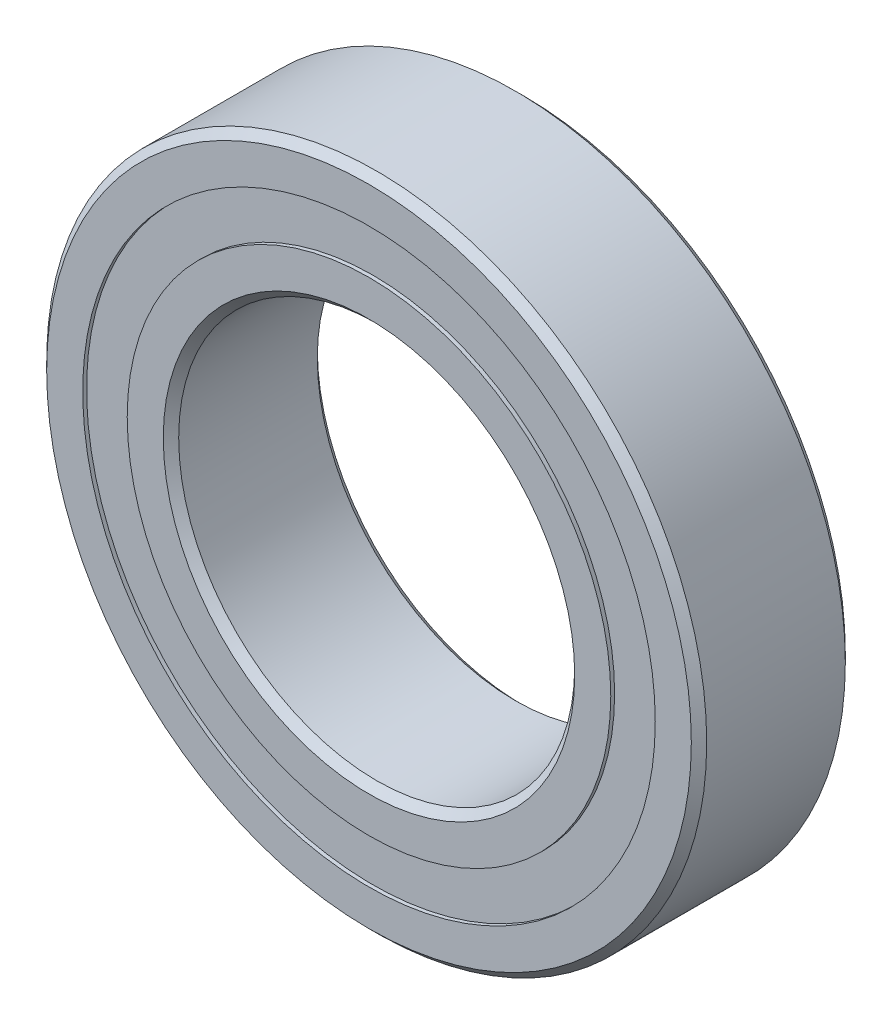
SolidWorks part; units mm, degrees
ref_plane "Front Plane" through (0, 0, 0) normal (0, 0, 1) x (1, 0, 0)
ref_plane "Top Plane" through (0, 0, 0) normal (0, 1, 0) x (1, 0, 0)
ref_plane "Right Plane" through (0, 0, 0) normal (1, 0, 0) x (0, 0, -1)
sketch "Sketch1" plane through (0, 0, 0) normal (1, 0, 0) x (0, 0, -1)
  line L0 (-3.5, 0) -> (3.5, 0) construction
  line L1 (0, 15) -> (0, -15) construction
  line L2 (3.15, 15) -> (-3.15, 15)
  line L3 (-3.15, 15) -> (-3.5, 14.65)
  line L4 (-3.5, 14.65) -> (-3.5, 13.011)
  line L5 (-3.5, 13.011) -> (-1.5556, 13.011)
  line L6 (3.5, 13.011) -> (1.5556, 13.011)
  line L7 (3.5, 14.65) -> (3.5, 13.011)
  line L8 (3.15, 15) -> (3.5, 14.65)
  line L9 (0, 15) -> (0, 12) construction
  line L10 (0, 12) -> (0, 9) construction
  arc A0 (-1.5556, 13.011) -> (1.5556, 13.011) centre (0, 12) cw
  point P14 (0, 9)
  dimension "Width" = 7
  dimension "OD" = 30
  dimension "D1" = 45
  dimension "D2" = 0.35
  dimension "Shaft Dia" = 18
  dimension "D3" = 3.1111
  dimension "D4" = 1.011
revolve "Revolve1" add sketch "Sketch1" angle 360 about L0
sketch "Sketch3" plane through (0, 0, 0) normal (1, 0, 0) x (0, 0, -1)
  line L0 (-3.5, 10.989) -> (-1.5556, 10.989)
  line L1 (0, 15) -> (0, -15) construction
  line L2 (-3.5, 14.65) -> (-3.5, 13.011) construction
  line L3 (-3.5, 10.989) -> (-3.5, 9.35)
  line L4 (-3.15, 15) -> (-3.5, 14.65) construction
  line L5 (-3.5, 9.35) -> (-3.15, 9)
  line L6 (-3.15, 9) -> (3.15, 9)
  line L7 (3.15, 15) -> (3.15, -15) construction
  line L8 (3.15, 9) -> (3.5, 9.35)
  line L9 (3.5, -14.65) -> (3.5, 14.65) construction
  line L10 (3.5, 9.35) -> (3.5, 10.989)
  line L11 (3.5, 10.989) -> (1.5556, 10.989)
  line L13 (3.15, 15) -> (3.5, 14.65) construction
  arc A0 (1.5556, 13.011) -> (-1.5556, 13.011) centre (0, 12) ccw construction
  arc A1 (1.5556, 10.989) -> (-1.5556, 10.989) centre (0, 12) cw
revolve "Revolve3" add sketch "Sketch3" angle 360 about L0
sketch "Sketch4" plane through (0, 0, 0) normal (1, 0, 0) x (0, 0, -1)
  line L0 (-1.8552, 12) -> (1.8552, 12)
  arc A2 (-1.8552, 12) -> (1.8552, 12) centre (0, 12) cw
  arc A3 (1.5556, 13.011) -> (-1.5556, 13.011) centre (0, 12) ccw construction
revolve "Revolve4" add sketch "Sketch4" angle 360 about L0
ref_axis "Axis1" through (0, 0, -3.5) along (0, 0, 1)
pattern_circular "CirPattern1" count 12 every 30 about axis through (0, 0, -3.5) along (0, 0, 1) of bodies 104
sketch "Sketch5" plane through (0, 0, 0) normal (1, 0, 0) x (0, 0, -1)
  line L0 (-3.5, 13.011) -> (-1.5556, 13.011) construction
  line L1 (-3.325, 13.011) -> (-1.8552, 13.011)
  line L2 (-3.325, 13.011) -> (-3.325, 10.989)
  line L3 (-3.325, 10.989) -> (-1.8552, 10.989)
  line L4 (-1.8552, 13.011) -> (-1.8552, 10.989)
  line L5 (-3.5, 10.989) -> (-1.5556, 10.989) construction
  line L6 (3.5, 13.011) -> (1.5556, 13.011) construction
  line L7 (3.325, 13.011) -> (1.8552, 13.011)
  line L8 (3.325, 13.011) -> (3.325, 10.989)
  line L9 (3.325, 10.989) -> (1.8552, 10.989)
  line L10 (1.8552, 13.011) -> (1.8552, 10.989)
  line L11 (3.5, 10.989) -> (1.5556, 10.989) construction
  line L12 (-3.15, 15) -> (-3.5, 14.65) construction
  point P18 (-3.325, 14.825)
revolve "Revolve5" add sketch "Sketch5" angle 360 about L0
equation "\"D2@Sketch1\" = \"Width@Sketch1\"*.05"
equation "\"D3@Sketch1\" = \"Width@Sketch1\"/2.25"
equation "\"D4@Sketch1\" = (((\"OD@Sketch1\"-\"Width@Sketch1\")/2)/3.25)/3.5"
equation "\"D2@CirPattern1\" = 360/\"Balls@CirPattern1\""
